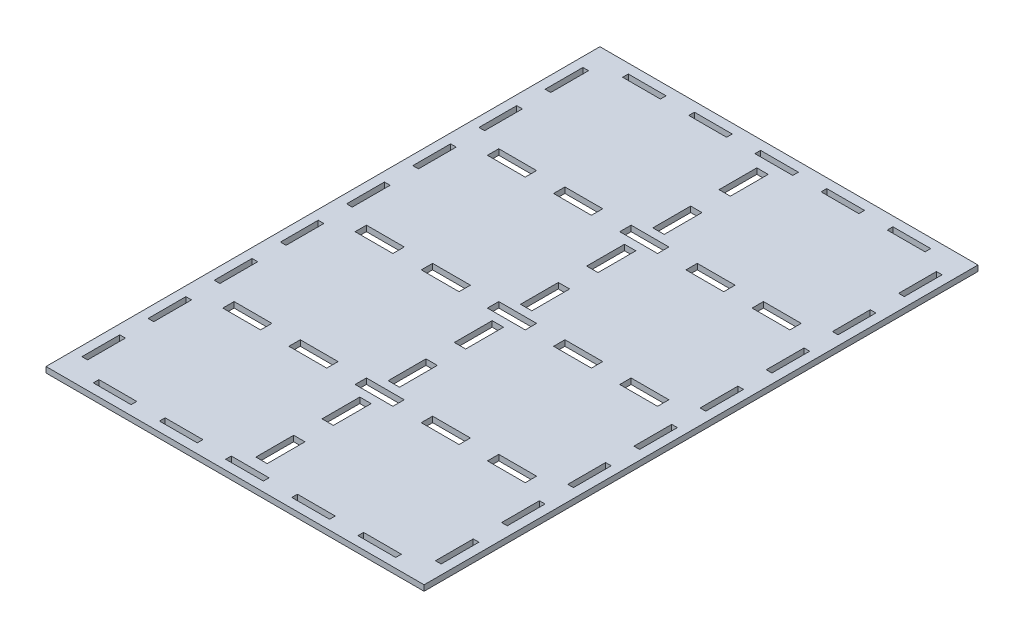
SolidWorks part; units mm, degrees
ref_plane "Front Plane" through (0, 0, 0) normal (0, 0, 1) x (1, 0, 0)
ref_plane "Top Plane" through (0, 0, 0) normal (0, 1, 0) x (1, 0, 0)
ref_plane "Right Plane" through (0, 0, 0) normal (1, 0, 0) x (0, 0, -1)
sketch "Sketch1" plane through (0, 0, 0) normal (0, 1, 0) x (1, 0, 0)
  line L1 (0, 0) -> (200, 0)
  line L2 (0, 0) -> (0, 293)
  line L3 (0, 293) -> (200, 293)
  line L4 (200, 0) -> (200, 293)
  line L5 (0, 0) -> (200, 293) construction
  line L6 (0, 293) -> (200, 0) construction
  line L7 (20, 288) -> (40, 288)
  line L8 (20, 288) -> (20, 285)
  line L9 (20, 285) -> (40, 285)
  line L10 (40, 288) -> (40, 285)
  line L11 (20, 288) -> (40, 285) construction
  line L12 (20, 285) -> (40, 288) construction
  line L13 (5, 279) -> (8, 279)
  line L14 (5, 279) -> (5, 259)
  line L15 (5, 259) -> (8, 259)
  line L16 (8, 279) -> (8, 259)
  line L17 (5, 279) -> (8, 259) construction
  line L18 (5, 259) -> (8, 279) construction
  line L38 (0, 146.5) -> (200, 146.5) construction
  line L39 (100, 293) -> (100, 0) construction
  point P10 (30, 286.5)
  point P15 (6.5, 269)
  dimension "D1" = 293
  dimension "D2" = 200
  dimension "D3" = 3
  dimension "D4" = 20
  dimension "D5" = 5
  dimension "D6" = 5
  dimension "D7" = 14
  dimension "D8" = 20
extrude "Boss-Extrude1" add sketch "Sketch1" along normal blind 3 contours L1 L4 L3 L2 L7 L10 L9 L8 L13 L16 L15 L14 | L10 L7 L8 L9 | L16 L13 L14 L15 region at (100.1677, 0, -146.2307) region at (30, 0, -286.5) region at (6.5, 0, -269)
sketch "Sketch2" plane through (0, 3, 0) normal (0, 1, 0) x (1, 0, 0)
  line L0 (5, 259) -> (8, 259) construction
  line L1 (8, 279) -> (8, 259) construction
  line L2 (5, 279) -> (5, 259) construction
  line L3 (5, 279) -> (8, 279) construction
  line L4 (8, 279) -> (5, 279)
  line L5 (8, 259) -> (8, 279)
  line L6 (5, 259) -> (8, 259)
  line L7 (5, 279) -> (5, 259)
  line L8 (8, 279) -> (5, 279)
  line L9 (8, 259) -> (8, 279)
  line L10 (5, 259) -> (8, 259)
  line L11 (5, 279) -> (5, 259)
  line L12 (40, 288) -> (20, 288)
  line L13 (40, 285) -> (40, 288)
  line L14 (20, 285) -> (40, 285)
  line L15 (20, 288) -> (20, 285)
  line L16 (40, 288) -> (20, 288)
  line L17 (40, 285) -> (40, 288)
  line L18 (20, 285) -> (40, 285)
  line L19 (20, 288) -> (20, 285)
  line L20 (0, 0) -> (200, 0)
  line L21 (200, 0) -> (200, 293)
  line L22 (200, 293) -> (0, 293)
  line L23 (0, 293) -> (0, 0)
  line L24 (0, 0) -> (200, 0)
  line L25 (200, 0) -> (200, 293)
  line L26 (200, 293) -> (0, 293)
  line L27 (0, 293) -> (0, 0)
  line L28 (20, 288) -> (20, 285) construction
  line L29 (40, 288) -> (40, 285) construction
  line L30 (20, 285) -> (40, 285) construction
  line L31 (20, 288) -> (40, 288) construction
  line L32 (5, 259) -> (8, 259)
  line L33 (8, 279) -> (8, 259)
  line L34 (5, 279) -> (5, 259)
  line L35 (5, 279) -> (8, 279)
  line L36 (20, 288) -> (20, 285)
  line L37 (40, 288) -> (40, 285)
  line L38 (20, 285) -> (40, 285)
  line L39 (20, 288) -> (40, 288)
  dimension "D1" = 0
  dimension "D2" = 0
  dimension "D3" = 0
extrude "Cut-Extrude2" cut sketch "Sketch2" against normal blind 10 contours L16 L19 L18 L17 | L8 L11 L10 L9 region at (6.5, 3, -269) region at (30, 3, -286.5)
pattern_linear "LPattern3" count 5 spacing 35 along (1, 0, 0) count 5 spacing 70 along (0, 0, 1) of face at (30, 1.5, -285) of face at (20, 1.5, -286.5) of face at (30, 1.5, -288) of face at (40, 1.5, -286.5)
pattern_linear "LPattern4" count 3 spacing 93.5 along (1, 0, 0) count 8 spacing 35 along (0, 0, 1) of face at (5, 1.5, -269) of face at (8, 1.5, -269) of face at (6.5, 1.5, -279) of face at (6.5, 1.5, -259)
sketch "Sketch4" plane through (0, 3, 0) normal (0, 1, 0) x (1, 0, 0)
  line L0 (20, 215) -> (40, 215) construction
  line L1 (6.5, 286.5) -> (100, 286.5)
  line L2 (6.5, 286.5) -> (6.5, 216.5)
  line L3 (6.5, 216.5) -> (100, 216.5)
  line L4 (100, 286.5) -> (100, 216.5)
  line L5 (20, 8) -> (20, 5) construction
  line L6 (5, 224) -> (8, 224) construction
  line L7 (100, 293) -> (100, 0) construction
  line L8 (40, 215) -> (40, 218) construction
  line L9 (6.5, 216.5) -> (100, 216.5)
  line L10 (6.5, 216.5) -> (6.5, 146.5)
  line L11 (6.5, 146.5) -> (100, 146.5)
  line L12 (100, 216.5) -> (100, 146.5)
  line L13 (20, 218) -> (20, 215) construction
  line L14 (40, 218) -> (20, 218) construction
  line L15 (6.5, 146.5) -> (100, 146.5)
  line L16 (6.5, 146.5) -> (6.5, 76.5)
  line L17 (6.5, 76.5) -> (100, 76.5)
  line L18 (100, 146.5) -> (100, 76.5)
  line L19 (20, 215) -> (40, 215)
  line L20 (40, 215) -> (40, 218)
  line L21 (6.5, 76.5) -> (100, 76.5)
  line L22 (6.5, 76.5) -> (6.5, 6.5)
  line L23 (6.5, 6.5) -> (100, 6.5)
  line L24 (100, 76.5) -> (100, 6.5)
  line L25 (20, 218) -> (20, 215)
  line L26 (40, 218) -> (20, 218)
  line L28 (20, 219.5) -> (40, 219.5)
  line L29 (20, 219.5) -> (20, 213.5)
  line L30 (20, 213.5) -> (40, 213.5)
  line L31 (40, 219.5) -> (40, 213.5)
  point P18 (20, 6.5)
  point P27 (30, 220.9155)
  point P28 (20, 216.5)
  dimension "D1" = 7.5
  dimension "D2" = 6
extrude "Cut-Extrude3" cut sketch "Sketch4" against normal blind 10 contours L28 L31 L30 L29
pattern_linear "LPattern5" count 5 spacing 35 along (1, 0, 0) count 3 spacing 70 along (0, 0, 1) of "Cut-Extrude3"
sketch "Sketch5" plane through (0, 3, 0) normal (0, 1, 0) x (1, 0, 0)
  line L0 (101.5, 279) -> (98.5, 279) construction
  line L1 (97, 279) -> (103, 279)
  line L2 (97, 279) -> (97, 259)
  line L3 (97, 259) -> (103, 259)
  line L4 (103, 279) -> (103, 259)
  line L5 (97, 279) -> (103, 259) construction
  line L6 (97, 259) -> (103, 279) construction
  line L7 (98.5, 259) -> (101.5, 259) construction
  line L8 (100, 293) -> (100, 0) construction
  point P4 (100, 269)
  point P11 (0, 0)
  dimension "D1" = 6
extrude "Cut-Extrude4" cut sketch "Sketch5" against normal blind 10
pattern_linear "LPattern6" count 8 spacing 35 along (0, 0, 1) of "Cut-Extrude4"
